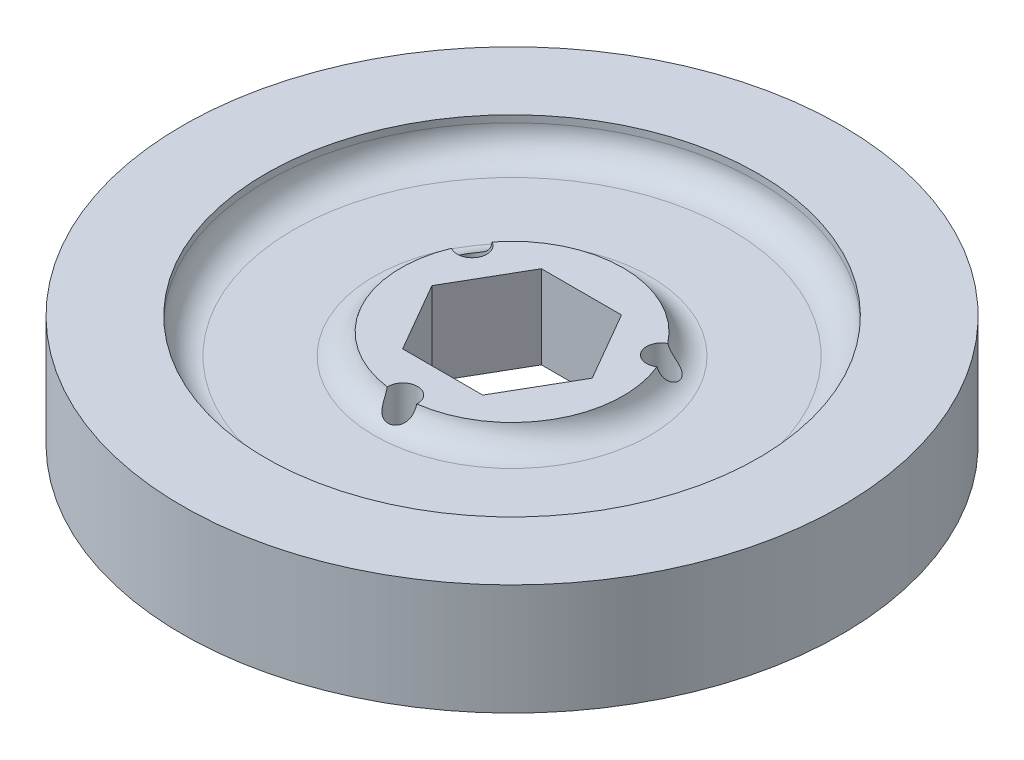
SolidWorks part; units mm, degrees
material "Rubber"
ref_plane "Front Plane" through (0, 0, 0) normal (0, 0, 1) x (1, 0, 0)
ref_plane "Top Plane" through (0, 0, 0) normal (0, 1, 0) x (1, 0, 0)
ref_plane "Right Plane" through (0, 0, 0) normal (1, 0, 0) x (0, 0, -1)
sketch "Sketch1" plane through (0, 0, 0) normal (0, 0, 1) x (1, 0, 0)
  line L0 (0, 0) -> (0, 9.2164) construction
  line L1 (10.16, -1.905) -> (10.16, -3.81)
  line L2 (0, 3.81) -> (10.16, 3.81)
  line L3 (0, 3.81) -> (0, -3.81)
  line L4 (0, -3.81) -> (10.16, -3.81)
  line L5 (10.16, 3.81) -> (10.16, 1.905)
  line L6 (10.16, 1.905) -> (22.5425, 1.905)
  line L7 (22.5425, -1.905) -> (22.5425, -5.08)
  line L8 (10.16, -1.905) -> (22.5425, -1.905)
  line L10 (22.5425, 5.08) -> (30.1625, 5.08)
  line L11 (22.5425, 5.08) -> (22.5425, 1.905)
  line L12 (22.5425, -5.08) -> (30.1625, -5.08)
  line L13 (30.1625, 5.08) -> (30.1625, -5.08)
  dimension "D1" = 7.62
  dimension "D2" = 10.16
  dimension "D3" = 3.81
  dimension "D4" = 22.5425
  dimension "D5" = 30.1625
  dimension "D6" = 10.16
revolve "Revolve1" add sketch "Sketch1" angle 360 about L0
fillet "Fillet1" radius 2.54 2 edges at (0, 1.905, -22.5425) (0, 1.905, -10.16)
fillet "Fillet2" radius 2.54 2 edges at (0, -1.905, -10.16) (0, -1.905, -22.5425)
sketch "Sketch2" plane through (0, -3.81, 0) normal (0, -1, 0) x (1, 0, 0)
  line L1 (3.6662, 6.35) -> (-3.6662, 6.35)
  line L2 (-3.6662, 6.35) -> (-7.3323, 0)
  line L3 (-7.3323, 0) -> (-3.6662, -6.35)
  line L4 (-3.6662, -6.35) -> (3.6662, -6.35)
  line L5 (3.6662, -6.35) -> (7.3323, 0)
  line L6 (7.3323, 0) -> (3.6662, 6.35)
  circle A0 centre (0, 0) radius 6.35 construction
  dimension "D1" = 12.7
extrude "Cut-Extrude1" cut sketch "Sketch2" against normal through all
hole_wizard "#6-32 Tapped Hole1" positions "Sketch3" profile "Sketch4" tap size "#6-32" standard "ANSI Inch" end condition through all
sketch "Sketch3" plane through (0, 3.81, 0) normal (0, 1, 0) x (1, 0, 0)
  point P0 (0, -10)
  point P3 (-8.6603, 5)
  point P6 (8.6603, 5)
sketch "Sketch4" plane through (0, 3.81, 10) normal (1, 0, 0) x (0, 0, 1)
  line L0 (0, 0) -> (0, 8.89)
  line L1 (0, 8.89) -> (1.3525, 8.89)
  line L2 (1.3525, 8.89) -> (1.3525, 0)
  line L5 (1.3525, 0) -> (0, 0)
  line L11 (0, -6.35) -> (0, 107.95) construction
  dimension "Thru Tap Drill Dia." = 2.7051
  dimension "Thru Tap Drill Depth" = 8.89
cosmetic thread "Hole Thread1" parameters "D2"=3.5052
cosmetic thread "Hole Thread2" parameters "D2"=3.5052
cosmetic thread "Hole Thread3" parameters "D2"=3.5052
